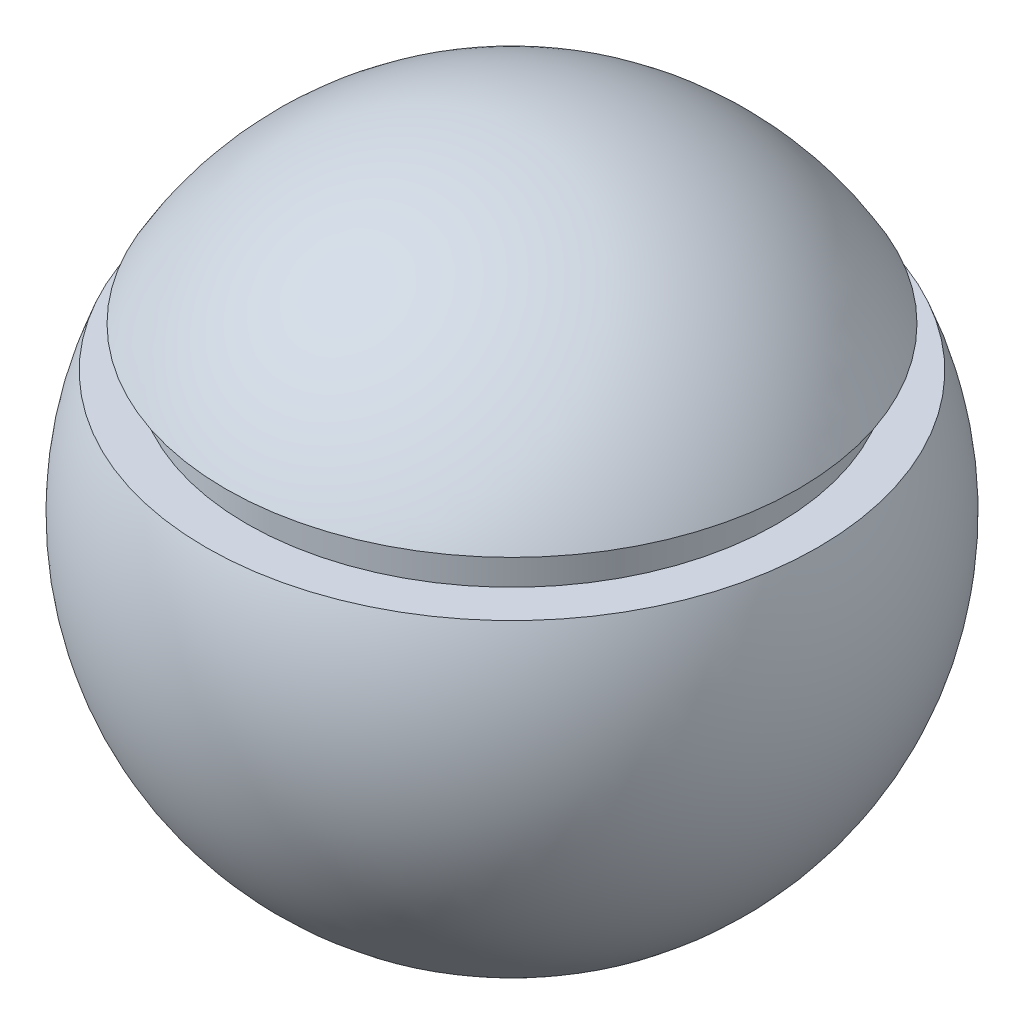
SolidWorks part; units mm, degrees
ref_plane "Front Plane" through (0, 0, 0) normal (0, 0, 1) x (1, 0, 0)
ref_plane "Top Plane" through (0, 0, 0) normal (0, 1, 0) x (1, 0, 0)
ref_plane "Right Plane" through (0, 0, 0) normal (1, 0, 0) x (0, 0, -1)
sketch "Sketch1" plane through (0, 0, 0) normal (0, 0, 1) x (1, 0, 0)
  line L0 (0, 10.2587) -> (0, -10.2587)
  line L1 (0, 0) -> (-16.4013, 0) construction
  line L2 (0, 0) -> (0, 17.7005) construction
  line L3 (-9.525, 3.81) -> (0, 3.81)
  arc A0 (0, 10.2587) -> (0, -10.2587) centre (0, 0) ccw
  point P8 (-9.525, 3.81)
  point P9 (0, 0)
  dimension "D1" = 9.525
  dimension "D2" = 3.81
revolve "Revolve1" add sketch "Sketch1" angle 360 about L0 region at (-3.79, 6.4747, 0) region at (-4.5616, -2.3841, 0)
sketch "Sketch2" plane through (0, 0, 0) normal (0, 0, 1) x (1, 0, 0)
  circle A0 centre (0, 0) radius 10.2587 construction
  point P0 (0, -10.2587)
ref_plane "Plane1" through (0, -10.2587, 0) normal (0, 1, 0) x (1, 0, 0)
sketch "Sketch3" plane through (0, -10.2587, 0) normal (0, 1, 0) x (1, 0, 0)
  circle A1 centre (0, 0) radius 3
  dimension "D1" = 6
extrude "Cut-Extrude1" cut sketch "Sketch3" along normal blind 12.7
thread "Thread1" pitch 1 method extrude profile "Thread Profile1" start angle 0, offset 0, length 8.89, pitch 1, diameter 6
ref_plane "Plane2" through (3, -9.8103, 0) normal (0, 0, 1) x (1, 0, 0)
sketch "Thread Profile1" plane through (3, -9.8103, 0) normal (0, 0, 1) x (1, 0, 0)
  line L0 (0, 0) -> (0, 1) construction
  line L11 (0, 0) -> (0, 0.875)
  line L12 (0, 0.875) -> (-0.5413, 0.5625)
  line L13 (-0.5413, 0.5625) -> (-0.5413, 0.3125)
  line L15 (-0.5413, 0.3125) -> (0, 0)
  line L17 (-0.5413, 0.4375) -> (0, 0.4375) construction
  point P2 (0, 0)
  dimension "Pitch" = 1
  dimension "Profile_Angle" = 60
  dimension "Profile_Land" = 0.25
  dimension "Profile_Height" = 0.5413
ref_plane "Plane3" through (0, 3.81, 0) normal (0, 1, 0) x (1, 0, 0)
sketch "Sketch8" plane through (0, 3.81, 0) normal (0, 1, 0) x (1, 0, 0)
  circle A0 centre (0, 0) radius 9.525
  circle A1 centre (0, 0) radius 8.255
  dimension "D1" = 19.05
  dimension "D2" = 1.27
extrude "Cut-Extrude2" cut sketch "Sketch8" along normal blind 1.27
